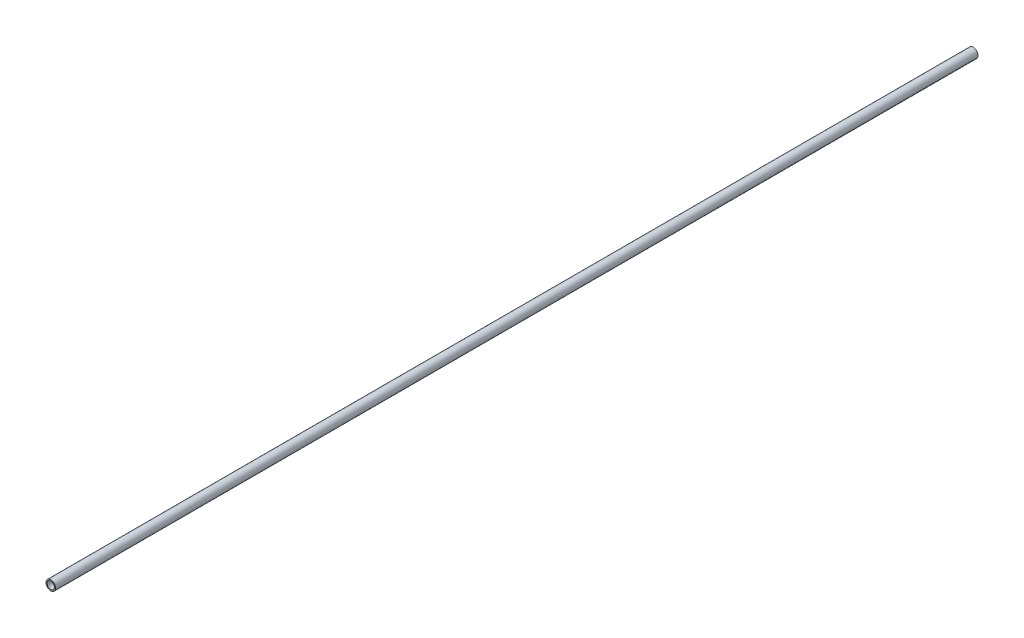
SolidWorks part; units mm, degrees
ref_plane "Front Plane" through (0, 0, 0) normal (0, 0, 1) x (1, 0, 0)
ref_plane "Top Plane" through (0, 0, 0) normal (0, 1, 0) x (1, 0, 0)
ref_plane "Right Plane" through (0, 0, 0) normal (1, 0, 0) x (0, 0, -1)
sketch "Sketch1" plane through (0, 0, 0) normal (0, 0, 1) x (1, 0, 0)
  circle A0 centre (0, 0) radius 6.35
  circle A1 centre (0, 0) radius 4.826
  dimension "D1" = 12.7
  dimension "D2" = 9.652
extrude "Boss-Extrude1" add sketch "Sketch1" along normal blind 1219.2
equation "\"span\" = 48"
equation "\"wing_chord\"= 9"
equation "\"fuse_len\"= 15"
equation "\"fuse_height\"= 5"
equation "\"fuse_wid\"= 5"
equation "\"foam_t\"= 0.1875"
equation "\"main_spar_len\"= 36"
equation "\"x_fuse_to_wing\"= 3"
equation "\"x_cg_from_le\"= 2.25"
equation "\"boom_len\"= 36"
equation "\"D1@Boss-Extrude1\"=\"wing_spar_l\""
equation "\"wing_spar_d\"= 0.5"
equation "\"wing_spar_spacing\"= 1.35"
equation "\"D1@Sketch1\"=\"wing_spar_d\""
equation "\"wing_spar_l\"= 48"
